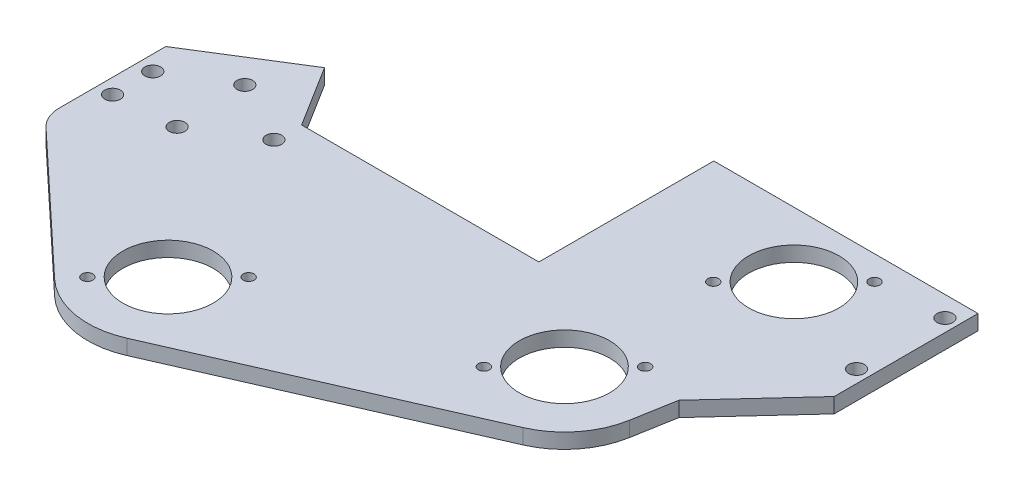
SolidWorks part; units mm, degrees
ref_plane "Front Plane" through (0, 0, 0) normal (0, 0, 1) x (1, 0, 0)
ref_plane "Top Plane" through (0, 0, 0) normal (0, 1, 0) x (1, 0, 0)
ref_plane "Right Plane" through (0, 0, 0) normal (1, 0, 0) x (0, 0, -1)
sketch "Sketch1" plane through (0, 0, 0) normal (0, 1, 0) x (1, 0, 0)
  line L1 (-62.0382, -79.8833) -> (25.1671, -41.6958)
  line L5 (39.9402, -22.8907) -> (42.2751, -9.5867)
  line L6 (42.2751, -9.5867) -> (65.831, 16.0128)
  line L12 (-135.7544, -31.9237) -> (-135.7544, 6.1763)
  line L16 (-92.7762, 6.1643) -> (-17.7344, 6.1643)
  line L17 (-135.7544, -31.9237) -> (-89.5888, -75.1562)
  line L19 (65.831, 61.4936) -> (-17.7344, 61.4936)
  line L20 (65.831, 16.0128) -> (65.831, 61.4936)
  line L22 (-17.7344, 61.4936) -> (-17.7344, 6.1643)
  line L23 (-135.7544, 6.1763) -> (-104.8504, 25.4872)
  line L24 (-191.7126, 164.4957) -> (-71.6498, -27.6449) construction
  line L25 (-104.8504, 25.4872) -> (-92.7762, 6.1643)
  line L26 (-72.2583, -56.6285) -> (15.031, -18.5085) construction
  line L27 (-72.2269, -82.0164) -> (109.3231, -82.0164) construction
  line L28 (15.0167, -18.5164) -> (15.0167, -82.0164) construction
  circle A0 centre (28.0466, 41.0458) radius 14.29
  circle A1 centre (15.031, -18.5085) radius 14.29
  circle A2 centre (-72.2583, -56.6285) radius 14.29
  arc A4 (39.9402, -22.8907) -> (25.1671, -41.6958) centre (15.0167, -18.5164) cw
  arc A6 (-62.0382, -79.8833) -> (-89.5888, -75.1562) centre (-72.2269, -56.6164) cw
  circle A7 centre (15.031, -18.5085) radius 25.4 construction
  circle A8 centre (-72.2583, -56.6285) radius 25.4 construction
  circle A9 centre (-28.6137, -37.5685) radius 22.225 construction
  circle A10 centre (28.0466, 41.0458) radius 30.48 construction
  circle A11 centre (15.031, -18.5085) radius 30.48 construction
  point P11 (-62.0382, -79.8833)
  point P34 (15.0167, -18.5164)
  point P35 (28.0466, 41.0458)
  dimension "D2" = 50.8
  dimension "D3" = 50.8
  dimension "D4" = 44.45
  dimension "D5" = 63.5
  dimension "D7" = 60.96
  dimension "D8" = 60.96
  dimension "D1" = 140.0048
  dimension "D6" = 95.25
  dimension "D9" = 50.8
  dimension "D10" = 143.51
extrude "Boss-Extrude1" add sketch "Sketch1" along normal blind 4.7625
fillet "Fillet1" radius 10 1 edges at (-135.7544, 2.3813, 31.9237)
hole_wizard "#10 Clearance Hole1" positions "Sketch2" profile "Sketch3" hole size "#10" standard "ANSI Inch" end condition through all
sketch "Sketch2" plane through (0, 4.7625, 0) normal (0, 1, 0) x (1, 0, 0)
  point P0 (61.8305, 55.0158)
  point P3 (61.8305, 27.0758)
  point P7 (-130.9919, -2.7257)
  point P10 (-130.9919, -15.4257)
sketch "Sketch3" plane through (61.8305, 4.7625, -55.0158) normal (1, 0, 0) x (0, 0, 1)
  line L0 (0, 0) -> (0, 4.7625)
  line L1 (0, 4.7625) -> (2.4892, 4.7625)
  line L2 (2.4892, 4.7625) -> (2.4892, 0)
  line L5 (2.4892, 0) -> (0, 0)
  line L11 (0, -6.35) -> (0, 107.95) construction
  dimension "Thru Hole Dia." = 4.9784
  dimension "Thru Hole Depth" = 4.7625
sketch "Sketch4" plane through (0, 4.7625, 0) normal (0, 1, 0) x (1, 0, 0)
  line L0 (-72.2583, -56.6285) -> (-102.5432, -8.1625) construction
  line L1 (-102.5432, -8.1625) -> (-93.1193, -2.2738) construction
  line L2 (-102.5432, -8.1625) -> (-111.9672, -14.0512) construction
  line L3 (-102.5432, -8.1625) -> (-112.7324, 8.1436) construction
  line L4 (-102.5432, -8.1625) -> (-174.2713, 106.6264) construction
  line L5 (65.831, 41.0458) -> (65.831, 28.3458) construction
  dimension "D1" = 57.15
  dimension "D2" = 22.225
  dimension "D3" = 32
hole_wizard "#10 Clearance Hole2" positions "Sketch5" profile "Sketch6" hole size "#10" standard "ANSI Inch" end condition through all
sketch "Sketch5" plane through (0, 4.7625, 0) normal (0, 1, 0) x (1, 0, 0)
  point P0 (-111.9672, -14.0512)
  point P3 (-93.1193, -2.2738)
  point P7 (-112.7324, 8.1436)
sketch "Sketch6" plane through (-111.9672, 4.7625, 14.0512) normal (1, 0, 0) x (0, 0, 1)
  line L0 (0, 0) -> (0, 4.7625)
  line L1 (0, 4.7625) -> (2.4892, 4.7625)
  line L2 (2.4892, 4.7625) -> (2.4892, 0)
  line L5 (2.4892, 0) -> (0, 0)
  line L11 (0, -6.35) -> (0, 107.95) construction
  dimension "Thru Hole Dia." = 4.9784
  dimension "Thru Hole Depth" = 4.7625
sketch "Sketch7" plane through (0, 4.7625, 0) normal (0, 1, 0) x (1, 0, 0)
  line L0 (-85.0103, -69.3804) -> (-59.5064, -43.8765) construction
  line L1 (2.279, -31.2604) -> (27.783, -5.7565) construction
  line L3 (15.2946, 28.2939) -> (40.7985, 53.7978) construction
  point P7 (-72.2583, -56.6285)
  point P11 (15.031, -18.5085)
  point P13 (28.0466, 41.0458)
hole_wizard "Tap Drill for #8-32 Tap1" positions "Sketch8" profile "Sketch9" hole size "#8-32" standard "ANSI Inch" end condition through all
sketch "Sketch8" plane through (0, 4.7625, 0) normal (0, 1, 0) x (1, 0, 0)
  point P0 (-59.5064, -43.8765)
  point P3 (-85.0103, -69.3804)
  point P6 (2.279, -31.2604)
  point P9 (27.783, -5.7565)
  point P12 (15.2946, 28.2939)
  point P15 (40.7985, 53.7978)
sketch "Sketch9" plane through (-59.5064, 4.7625, 43.8765) normal (1, 0, 0) x (0, 0, 1)
  line L0 (0, 0) -> (0, 4.7625)
  line L1 (0, 4.7625) -> (1.7272, 4.7625)
  line L2 (1.7272, 4.7625) -> (1.7272, 0)
  line L5 (1.7272, 0) -> (0, 0)
  line L11 (0, -6.35) -> (0, 107.95) construction
  dimension "Thru Hole Dia." = 3.4544
  dimension "Thru Hole Depth" = 4.7625
